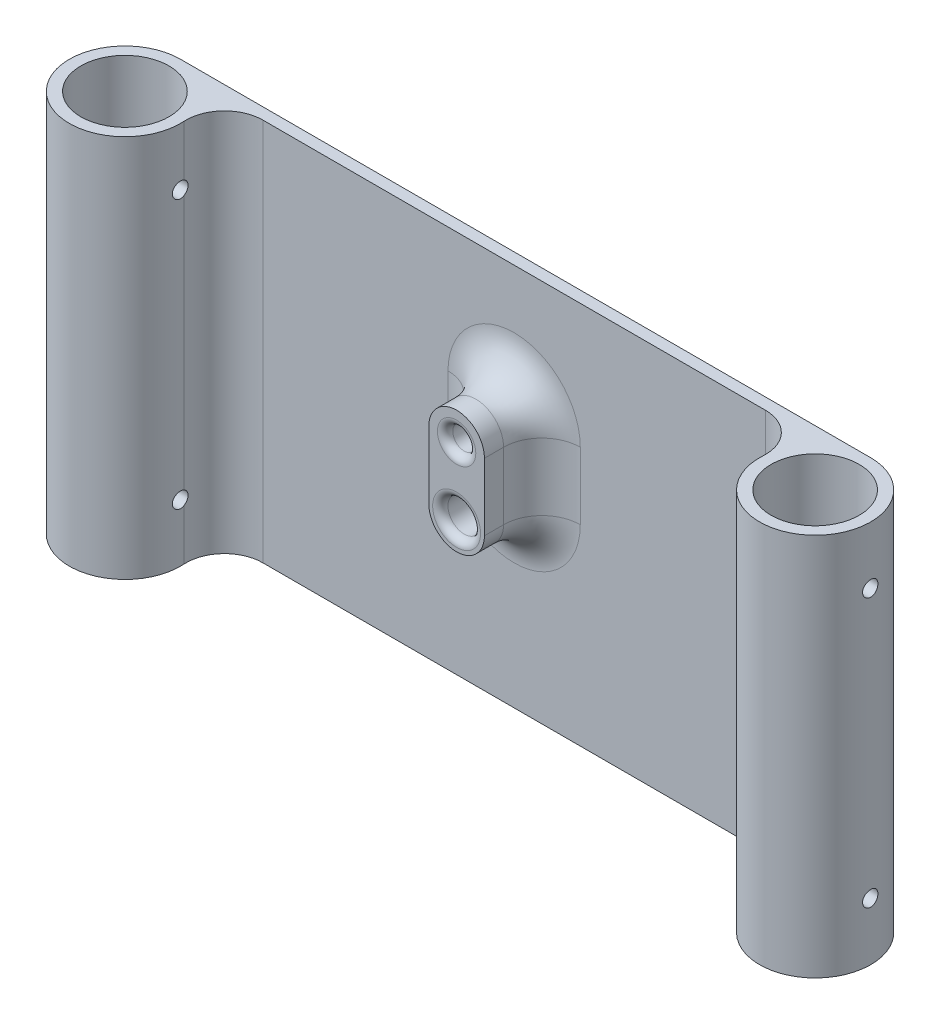
SolidWorks part; units mm, degrees
ref_plane "Front Plane" through (0, 0, 0) normal (0, 0, 1) x (1, 0, 0)
ref_plane "Top Plane" through (0, 0, 0) normal (0, 1, 0) x (1, 0, 0)
ref_plane "Right Plane" through (0, 0, 0) normal (1, 0, 0) x (0, 0, -1)
sketch "Sketch1" plane through (0, 0, 0) normal (0, 1, 0) x (1, 0, 0)
  line L3 (-42.5394, 14.5) -> (137.4606, 14.5)
  line L4 (128.6288, 11.5) -> (-33.7077, 11.5)
  circle A0 centre (-42.5394, 0) radius 11.5
  circle A1 centre (137.4606, 0) radius 11.5
  arc A2 (-28.3532, -3) -> (-42.5394, 14.5) centre (-42.5394, 0) cw
  arc A3 (123.2743, 3) -> (128.6288, 11.5) centre (137.4606, 0) cw
  arc A4 (-28.3532, -3) -> (-28.3532, 3) centre (-42.5394, 0) ccw
  arc A5 (123.2743, -3) -> (123.2743, 3) centre (137.4606, 0) cw
  arc A6 (137.4606, 14.5) -> (123.2743, -3) centre (137.4606, 0) cw
  arc A7 (-33.7077, 11.5) -> (-28.3532, 3) centre (-42.5394, 0) cw
  dimension "D3" = 23
  dimension "D4" = 23
  dimension "D5" = 180
  dimension "D6" = 3
  dimension "D7" = 3
  dimension "D8" = 3
extrude "Boss-Extrude1" add sketch "Sketch1" along normal blind 100
fillet "Fillet1" radius 10 1 edges at (-33.7077, 50, -11.5)
fillet "Fillet2" radius 10 1 edges at (128.6288, 50, -11.5)
sketch "Sketch3" plane through (0, 0, -14.5) normal (0, 0, -1) x (-1, 0, 0)
  line L0 (-47.4606, 0) -> (-47.4606, 100) construction
  line L1 (-137.4606, 0) -> (42.5394, 0) construction
  line L2 (-137.4606, 100) -> (42.5394, 100) construction
sketch "Sketch2" plane through (0, 0, -11.5) normal (0, 0, 1) x (1, 0, 0)
  line L0 (47.4606, 0) -> (47.4606, 100) construction
  circle A0 centre (47.4606, 50) radius 4.25
  circle A1 centre (47.4606, 67.5) radius 3
  point P0 (47.4606, 67.5)
  point P3 (47.4606, 50)
  dimension "D1" = 8.5
  dimension "D2" = 6
  dimension "D3" = 17.5
extrude "Cut-Extrude1" cut sketch "Sketch2" against normal blind 10
sketch "Sketch4" plane through (0, 0, -11.5) normal (0, 0, 1) x (1, 0, 0)
  line L0 (40.2106, 50) -> (40.2106, 67.5)
  line L1 (54.7106, 67.5) -> (54.7106, 50)
  circle A0 centre (47.4606, 50) radius 4.25
  arc A1 (40.2106, 50) -> (54.7106, 50) centre (47.4606, 50) ccw
  circle A2 centre (47.4606, 67.5) radius 3
  arc A3 (54.7106, 67.5) -> (40.2106, 67.5) centre (47.4606, 67.5) ccw
  circle A6 centre (47.4606, 50) radius 4.25 construction
  circle A7 centre (47.4606, 67.5) radius 3 construction
  point P3 (54.8809, 16.1594)
  dimension "D1" = 3
extrude "Boss-Extrude2" add sketch "Sketch4" along normal blind 15
sketch "Sketch5" plane through (0, 0, -14.5) normal (0, 0, -1) x (-1, 0, 0)
  circle A0 centre (-47.4606, 50) radius 7.25
  dimension "D1" = 14.5
extrude "Boss-Extrude3" add sketch "Sketch5" along normal blind 10
sketch "Sketch6" plane through (0, 0, -14.5) normal (0, 0, -1) x (-1, 0, 0)
  circle A0 centre (-47.4606, 50) radius 12.1093
extrude "Boss-Extrude4" add sketch "Sketch6" along normal blind 1
fillet "Fillet3" radius 2 1 edges at (40.2106, 50, -24.5)
ref_plane "Plane1" through (-42.5394, 0, 0) normal (1, 0, 0) x (0, 0, -1)
sketch "Sketch7" plane through (-42.5394, 0, 0) normal (1, 0, 0) x (0, 0, -1)
  line L0 (14.5, 100) -> (-14.5, 100) construction
  line L1 (-14.5, 0) -> (14.5, 0) construction
  circle A0 centre (0, 15) radius 2
  circle A1 centre (0, 85) radius 2
  dimension "D1" = 4
  dimension "D2" = 4
  dimension "D3" = 15
  dimension "D4" = 15
extrude "Cut-Extrude2" cut sketch "Sketch7" against normal through all both and the other way through all
fillet "Fillet4" radius 2 2 edges at (50.4606, 67.5, 3.5) (51.7106, 50, 3.5)
fillet "Fillet5" radius 2 1 edges at (59.5699, 50, -14.5)
fillet "Fillet6" radius 10 4 edges at (54.7106, 58.75, -11.5) (47.4606, 42.75, -11.5) (40.2106, 58.75, -11.5) (47.4606, 74.75, -11.5)
